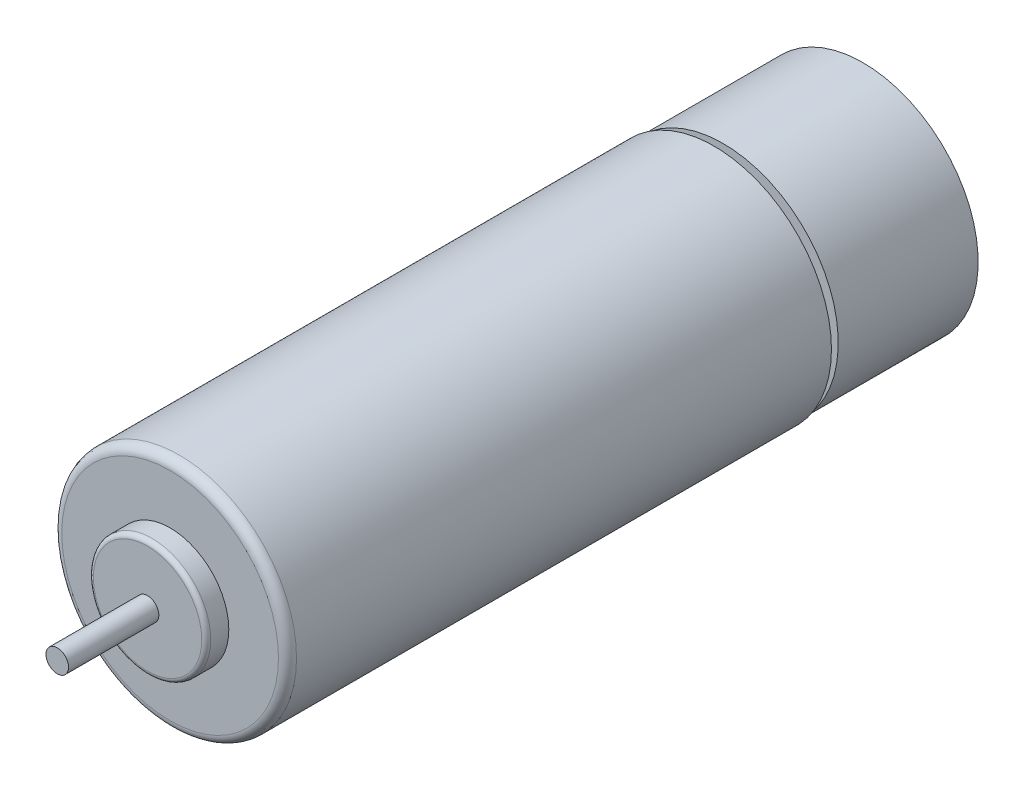
SolidWorks part; units mm, degrees
material "6061 合金"
ref_plane "前视基准面" through (0, 0, 0) normal (0, 0, 1) x (1, 0, 0)
ref_plane "上视基准面" through (0, 0, 0) normal (0, 1, 0) x (1, 0, 0)
ref_plane "右视基准面" through (0, 0, 0) normal (1, 0, 0) x (0, 0, -1)
sketch "草图1" plane through (0, 0, 0) normal (0, 0, 1) x (1, 0, 0)
  circle A0 centre (0, 0) radius 26
  dimension "D1" = 52
extrude "凸台-拉伸1" add sketch "草图1" along normal blind 120.5
ref_plane "基准面1" through (0, 0, -2) normal (0, 0, -1) x (-1, 0, 0)
sketch "草图2" plane through (0, 0, 120.5) normal (0, 0, 1) x (1, 0, 0)
  circle A0 centre (0, 0) radius 13
  dimension "D1" = 26
extrude "凸台-拉伸2" add sketch "草图2" along normal blind 5
sketch "草图3" plane through (0, 0, 125.5) normal (0, 0, 1) x (1, 0, 0)
  circle A0 centre (0, 0) radius 2.5
  dimension "D1" = 5
extrude "凸台-拉伸3" add sketch "草图3" along normal blind 20
sketch "草图7" plane through (0, 0, 0) normal (0, 0, -1) x (-1, 0, 0)
  circle A0 centre (0, 0) radius 2.5 construction
  circle A1 centre (0, 0) radius 2.5
extrude "凸台-拉伸7" add sketch "草图7" along normal blind 25
fillet "圆角2" radius 2 1 edges at (26, 0, 120.5)
fillet "圆角3" radius 1 1 edges at (13, 0, 125.5)
sketch "草图4" plane through (0, 0, -2) normal (0, 0, -1) x (-1, 0, 0)
  circle A0 centre (0, 0) radius 25.5
  circle A1 centre (0, 0) radius 22.5
  dimension "D1" = 51
  dimension "D2" = 45
extrude "凸台-拉伸4" add sketch "草图4" along normal blind 28 separate body
sketch "草图5" plane through (0, 0, -30) normal (0, 0, -1) x (-1, 0, 0)
  circle A0 centre (0, 0) radius 25.5 construction
  circle A1 centre (0, 0) radius 25.5
  circle A2 centre (0, 0) radius 17.5
  dimension "D1" = 35
extrude "凸台-拉伸5" add sketch "草图5" along normal blind 3
sketch "草图6" plane through (0, 0, -33) normal (0, 0, -1) x (-1, 0, 0)
  line L0 (0, 0) -> (0, 25.5) construction
  line L1 (-1, 3.8773) -> (-2, 25.4214)
  line L2 (1, 3.8773) -> (2, 25.4214)
  circle A0 centre (0, 0) radius 25.5 construction
  arc A1 (2, 25.4214) -> (-2, 25.4214) centre (0, 0) ccw
  arc A2 (-1, 3.8773) -> (1, 3.8773) centre (0, 0) ccw
  circle A3 centre (0, 0) radius 2.5 construction
  circle A4 centre (0, 0) radius 2.5
  dimension "D1" = 1
  dimension "D2" = 2
extrude "凸台-拉伸6" add sketch "草图6" against normal up to surface (31 mm away) up to face at (-25.5, 0, -2)
ref_axis "基准轴1" through (0, 0, -40.4) along (0, 0, 1)
pattern_circular "阵列(圆周)1" count 6 over 360 about axis through (0, 0, -40.4) along (0, 0, 1) of "凸台-拉伸6"
